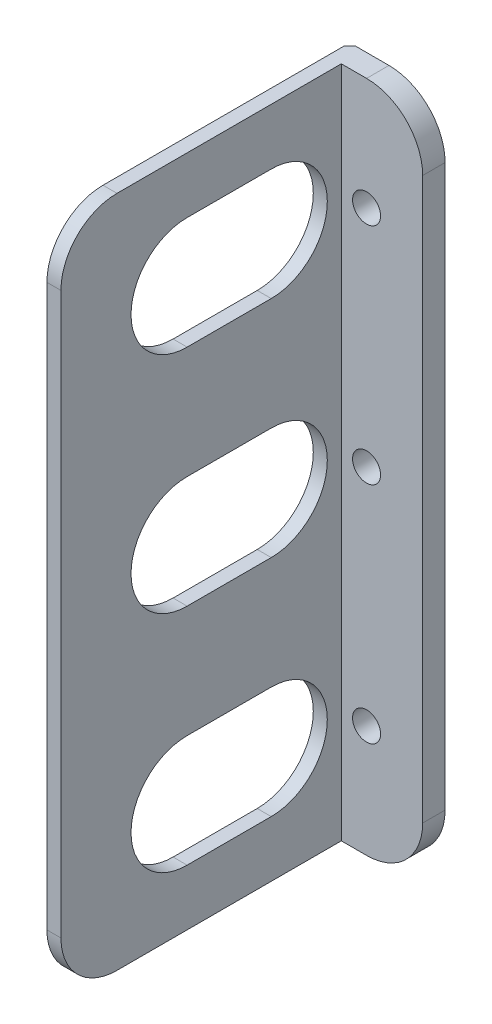
SolidWorks part; units mm, degrees
ref_plane "정면" through (0, 0, 0) normal (0, 0, 1) x (1, 0, 0)
ref_plane "윗면" through (0, 0, 0) normal (0, 1, 0) x (1, 0, 0)
ref_plane "우측면" through (0, 0, 0) normal (1, 0, 0) x (0, 0, -1)
sketch "스케치1" plane through (0, 0, 0) normal (0, 0, 1) x (1, 0, 0)
  line L0 (0, 60) -> (0, -60) construction
  line L1 (-10, 60) -> (10, 60)
  line L2 (-10, 60) -> (-10, -60)
  line L3 (-10, -60) -> (10, -60)
  line L4 (10, 60) -> (10, -60)
  line L5 (-10, 60) -> (10, -60) construction
  line L6 (-10, -60) -> (10, 60) construction
  line L7 (-10, 60) -> (-7, 60)
  line L8 (-10, 60) -> (-10, -60)
  line L9 (-10, -60) -> (-7, -60)
  line L10 (-7, 60) -> (-7, -60)
  line L11 (-7, 60) -> (-4.5, 60)
  line L12 (-7, 60) -> (-7, -60)
  line L13 (-7, -60) -> (-4.5, -60)
  line L14 (-4.5, 60) -> (-4.5, -60)
  circle A0 centre (0, 0) radius 2.5
  circle A1 centre (0, 40) radius 2.5
  circle A2 centre (0, -40) radius 2.5
  circle A3 centre (0, -40) radius 3.5 construction
  point P0 (0, 0)
  dimension "D5" = 5
  dimension "D6" = 5
  dimension "D7" = 5
  dimension "D10" = 7
  dimension "D1" = 3
  dimension "D2" = 20
  dimension "D3" = 2.5
  dimension "D4" = 120
  dimension "D8" = 20
  dimension "D9" = 20
extrude "보스-돌출1" add sketch "스케치1" against normal blind 4 contours L1 L14 L3 L4 A2 A1 A0 | L14 L1 L10 L3 region at (-5.75, 0, 0) region at (2.8464, 0, 0)
extrude "보스-돌출2" add sketch "스케치1<3>" along normal blind 50 contours L14 L1 L10 L3 region at (-5.75, 0, 0)
sketch "스케치1<3>" plane through (0, 0, 0) normal (0, 0, 1) x (1, 0, 0) same geometry as "스케치1"
fillet "필렛1" radius 10 4 edges at (10, -60, -2) (10, 60, -2) (-5.75, 60, 50) (-5.75, -60, 50)
sketch "스케치2" plane through (-4.5, 0, 0) normal (1, 0, 0) x (0, 0, -1)
  line L0 (-20, -60) -> (-20, 60) construction
  line L1 (-40, -60) -> (0, -60) construction
  line L2 (-40, 60) -> (0, 60) construction
  line L3 (-12.5, -40) -> (-27.5, -40) construction
  line L4 (-12.5, -50) -> (-27.5, -50)
  line L5 (-12.5, -30) -> (-27.5, -30)
  line L6 (-12.5, 0) -> (-27.5, 0) construction
  line L7 (-12.5, -10) -> (-27.5, -10)
  line L8 (-12.5, 10) -> (-27.5, 10)
  line L9 (-12.5, 40) -> (-27.5, 40) construction
  line L10 (-12.5, 30) -> (-27.5, 30)
  line L11 (-12.5, 50) -> (-27.5, 50)
  arc A0 (-12.5, -50) -> (-12.5, -30) centre (-12.5, -40) ccw
  arc A1 (-27.5, -30) -> (-27.5, -50) centre (-27.5, -40) ccw
  arc A2 (-12.5, -10) -> (-12.5, 10) centre (-12.5, 0) ccw
  arc A3 (-27.5, 10) -> (-27.5, -10) centre (-27.5, 0) ccw
  arc A4 (-12.5, 30) -> (-12.5, 50) centre (-12.5, 40) ccw
  arc A5 (-27.5, 50) -> (-27.5, 30) centre (-27.5, 40) ccw
  point P8 (-20, -40)
  point P14 (-20, 0)
  point P22 (-20, 40)
  dimension "D1" = 20
  dimension "D2" = 20
  dimension "D3" = 20
  dimension "D4" = 15
  dimension "D5" = 15
  dimension "D6" = 15
  dimension "D7" = 40
  dimension "D8" = 40
extrude "컷-돌출1" cut sketch "스케치2" against normal blind 50
chamfer "모따기1" distance 1 angle 45 1 edges at (-7, 0, -4)
